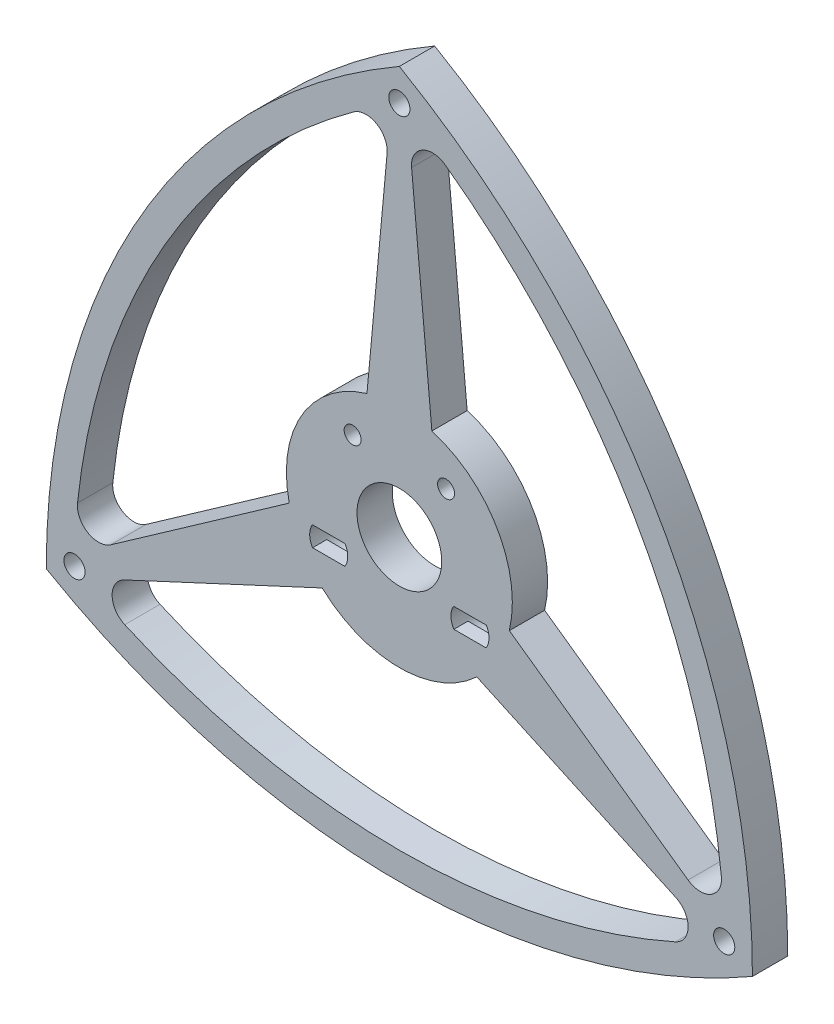
SolidWorks part; units mm, degrees
ref_plane "前视基准面" through (0, 0, 0) normal (0, 0, 1) x (1, 0, 0)
ref_plane "上视基准面" through (0, 0, 0) normal (0, 1, 0) x (1, 0, 0)
ref_plane "右视基准面" through (0, 0, 0) normal (1, 0, 0) x (0, 0, -1)
other "Configuration Table"
sketch "草图1" plane through (0, 0, 0) normal (0, 0, 1) x (1, 0, 0)
  line L0 (-50, -28.8675) -> (-13.8564, -8) construction
  line L10 (5.1962, 3) -> (5.7195, 3.3022) construction
  line L24 (-5.4164, 9.2323) -> (-5.2336, 9.2323) construction
  line L25 (50, -28.8675) -> (13.8564, -8) construction
  line L29 (-10, -4.6277) -> (-7.6811, -4.6277)
  line L30 (-10, -7.4346) -> (-7.7191, -7.4346)
  line L31 (-10, -4.6277) -> (-12.3189, -4.6277)
  line L32 (-10, -7.4346) -> (-12.2809, -7.4346)
  line L33 (7.6811, -4.6277) -> (12.3189, -4.6277)
  line L34 (7.7191, -7.4346) -> (12.2809, -7.4346)
  line L35 (-5.6123, 3.2403) -> (-5.7297, 3.308) construction
  line L36 (0, 57.735) -> (0, -6) construction
  line L37 (-50, -28.8675) -> (-46, -26.5581) construction
  line L38 (50, -28.8675) -> (46, -26.5581) construction
  line L39 (0, 57.735) -> (0, 53.735) construction
  line L40 (-46.0986, -26.615) -> (-42.2015, -24.365) construction
  line L41 (46.0986, -26.615) -> (42.2015, -24.365) construction
  line L42 (0, 53.2301) -> (0, 48.7301) construction
  line L43 (-40.8672, -21.3667) -> (-15.5866, -3.6138)
  line L44 (-38.9383, -24.7084) -> (-10.923, -11.6913)
  line L45 (39.1417, -24.6087) -> (10.9679, -11.6493)
  line L46 (40.8826, -21.5933) -> (15.5725, -3.6738)
  line L47 (-1.7328, 46.209) -> (-4.5844, 15.3292)
  line L48 (1.7344, 46.2064) -> (4.6026, 15.3237)
  line L49 (-5.7297, 3.308) -> (-5.6921, 3.3345)
  line L50 (0, -6.616) -> (0.0127, -6.6101)
  line L51 (0.0127, -6.6101) -> (0, -6.6043)
  line L52 (0, -6.6043) -> (0, -42.265) construction
  line L53 (5.7195, 3.3022) -> (5.7191, 3.3024)
  line L54 (-5.8985, 1.0988) -> (-6, 0)
  line L55 (13.8564, 8) -> (36.6025, 21.1325) construction
  line L56 (-5.6921, 3.3345) -> (-5.6963, 3.2888)
  line L57 (-13.8564, 8) -> (-36.6025, 21.1325) construction
  line L58 (-8.0154, -4.6277) -> (-7.7707, -4.4864) construction
  line L59 (8.0154, -4.6277) -> (7.7707, -4.4864) construction
  arc A4 (-6.4829, 48.9123) -> (-45.5741, -18.5909) centre (50, -28.8675) ccw
  arc A5 (50, -28.8675) -> (0, 57.735) centre (-50, -28.8675) ccw
  arc A6 (0, 57.735) -> (-50, -28.8675) centre (50, -28.8675) ccw
  arc A7 (-50, -28.8675) -> (50, -28.8675) centre (0, 57.735) ccw
  arc A11 (-4.3249, 15.4862) -> (-15.7368, -3.2987) centre (0, 0) ccw
  arc A12 (-38.8879, -30.1726) -> (39.1085, -30.0746) centre (0, 57.735) ccw
  arc A13 (45.5997, -18.8317) -> (6.4844, 48.9112) centre (-50, -28.8675) ccw
  circle A14 centre (-6.6164, 9.2323) radius 1.2
  circle A20 centre (-6.6164, 9.2323) radius 2.1
  circle A21 centre (6.6164, 9.2323) radius 2.1
  circle A22 centre (0, 0) radius 6
  circle A30 centre (6.6164, 9.2323) radius 1.2
  circle A31 centre (-10, -6) radius 2.6945
  circle A32 centre (10, -6) radius 2.6945
  arc A37 (-14.0672, -7.7873) -> (-13.6242, -8.5386) centre (0, 0) ccw
  arc A39 (15.5871, -3.9458) -> (4.3249, 15.4862) centre (0, 0) ccw
  arc A40 (13.5562, -8.6463) -> (14.0105, -7.8889) centre (0, 0) ccw
  circle A41 centre (0, 0) radius 16
  circle A43 centre (-46, -26.5581) radius 1.5
  circle A44 centre (46, -26.5581) radius 1.5
  circle A48 centre (0, 53.2301) radius 1.5
  circle A52 centre (-42.1331, -24.3256) radius 1.6939 construction
  circle A53 centre (42.2015, -24.365) radius 1.5 construction
  circle A54 centre (0, 48.7301) radius 1.5 construction
  arc A55 (0, 53.2301) -> (-46.0986, -26.615) centre (50, -28.8675) ccw construction
  arc A56 (-40.8672, -21.3667) -> (-45.5741, -18.5909) centre (-42.5913, -18.9116) cw
  arc A57 (46.0986, -26.615) -> (0, 53.2301) centre (-50, -28.8675) ccw construction
  arc A58 (1.7344, 46.2064) -> (6.4844, 48.9112) centre (4.7215, 46.4838) cw
  arc A59 (-1.7328, 46.209) -> (-6.4829, 48.9123) centre (-4.7201, 46.4848) ccw
  arc A60 (45.5997, -18.8317) -> (40.8826, -21.5933) centre (42.6161, -19.1449) cw
  arc A61 (-46.0986, -26.615) -> (46.0986, -26.615) centre (0, 57.735) ccw construction
  arc A62 (39.1085, -30.0746) -> (39.1417, -24.6087) centre (37.888, -27.3342) ccw
  arc A63 (-38.8879, -30.1726) -> (-38.9383, -24.7084) centre (-37.6742, -27.429) cw
  point P30 (-8.8405, -4.6277)
  dimension "D1" = 3.875
  dimension "D3" = 100
  dimension "D4" = 100
  dimension "D5" = 3
  dimension "D6" = 3
  dimension "D7" = 3
  dimension "D8" = 3
  dimension "D11" = 3
  dimension "D12" = 3
  dimension "D13" = 3
  dimension "D9" = 3
  dimension "D10" = 3
  dimension "D14" = 12
  dimension "D15" = 32
  dimension "D16" = 4.5049
  dimension "D17" = 4.5049
  dimension "D18" = 4.5049
  dimension "D2" = 100
extrude "凸台-拉伸3" add sketch "草图1" along normal blind 5 contours A6 A7 A5 A48 A44 A43 A12 A63 L44 A41 L43 A56 A4 A59 L47 L48 A58 A13 A60 L46 L45 A62 | A41 A20 A21 A22 A31 A32 | A20 A14 | A21 A30 | L32 A31 L30 | L29 A31 L31 | L33 A32 | L34 A32 region at (-10, -4.0858, 0) region at (-10, -7.9503, 0) region at (10, -4.0858, 0) region at (10, -7.9503, 0) region at (-13.4443, 7.8085, 0) region at (0, -40.8508, 0) region at (-8.657, 9.2323, 0) region at (4.5758, 9.2323, 0)
extrude "切除-拉伸1" cut sketch "草图1<128>" along normal blind 3 contours A20 | A21 | A31 | A32
sketch "草图1<128>" plane through (0, 0, 0) normal (0, 0, 1) x (1, 0, 0) same geometry as "草图1"
